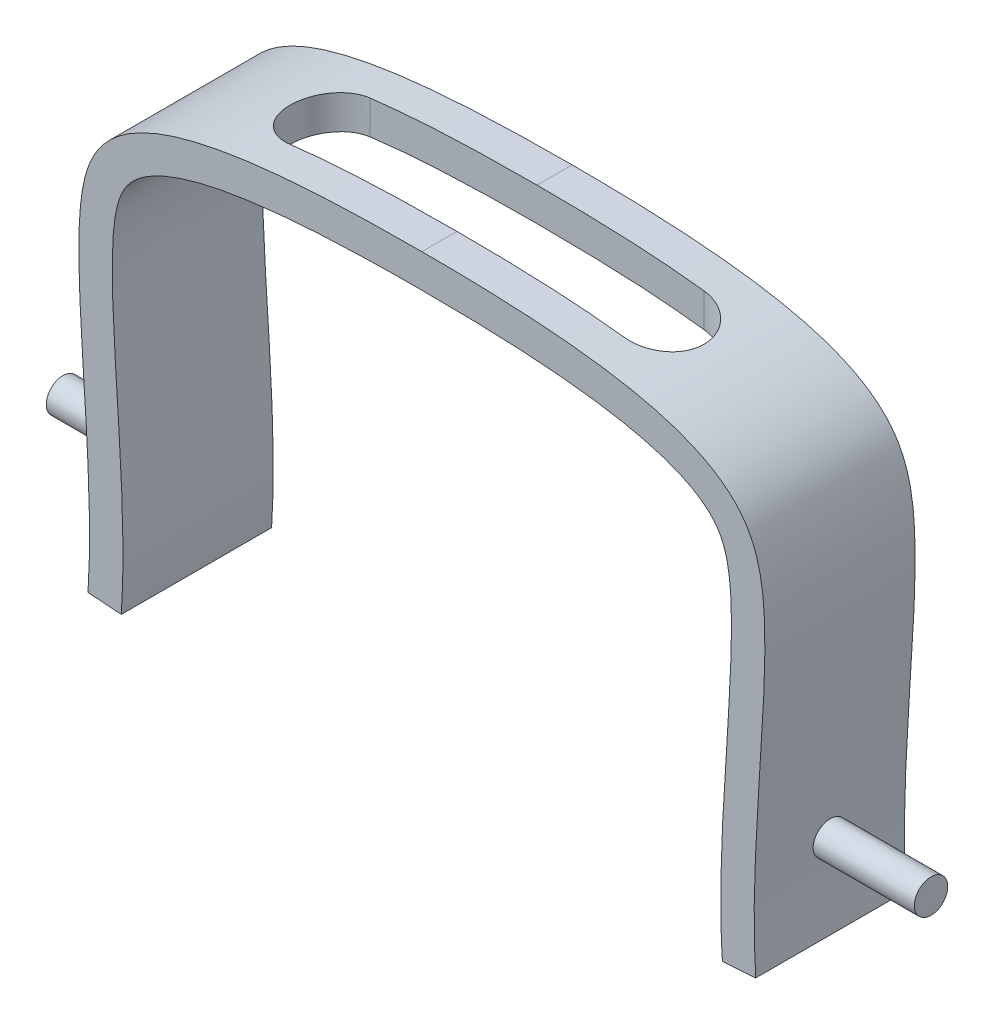
SolidWorks part; units mm, degrees
ref_plane "Front Plane" through (0, 0, 0) normal (0, 0, 1) x (1, 0, 0)
ref_plane "Top Plane" through (0, 0, 0) normal (0, 1, 0) x (1, 0, 0)
ref_plane "Right Plane" through (0, 0, 0) normal (1, 0, 0) x (0, 0, -1)
sketch "Sketch3" plane through (0, 0, 0) normal (0, 0, 1) x (1, 0, 0)
  line L0 (-25.3926, 0.4128) -> (-22.8588, 0.2357)
  line L1 (0, 0) -> (0, 49.1985) construction
  line L2 (22.8588, 0.2357) -> (25.3926, 0.4128)
  spline S0 degree 3 poles (-22.8588, 0.2357) (-22.2073, 9.561) (-24.8571, 24.7477) (-20.4286, 32.2593) (-9.2595, 33.02) (0, 33.02) knots 0 0 0 0 0.433889 0.533889 1 1 1 1
  spline S1 degree 1 poles (-25.3926, 0.4128) (0, 35.56) knots 0 0 1 1 construction
  spline S2 degree 3 poles (22.8588, 0.2357) (22.2073, 9.561) (24.8571, 24.7477) (20.4286, 32.2593) (9.2595, 33.02) (0, 33.02) knots 0 0 0 0 0.433889 0.533889 1 1 1 1
  spline S3 degree 1 poles (25.3926, 0.4128) (0, 35.56) knots 0 0 1 1 construction
  spline S4 degree 3 poles (-25.3926, 0.4128) (-25.3472, 1.0633) (-25.2873, 2.3429) (-25.2559, 5.0926) (-25.3636, 8.6726) (-25.623, 13.0382) (-25.906, 17.2716) (-26.1042, 21.2032) (-26.0979, 24.6856) (-25.8161, 27.1655) (-25.2212, 28.9768) (-24.5105, 30.2231) (-23.5816, 31.2478) (-22.1911, 32.3246) (-20.1914, 33.3182) (-17.4516, 34.1574) (-13.3644, 34.9503) (-8.7163, 35.3649) (-3.7754, 35.5373) (-1.2543, 35.56) (0, 35.56) knots 0 0 0 0 0.03125 0.0625 0.125 0.1875 0.25 0.3125 0.375 0.4375 0.46875 0.5 0.53125 0.5625 0.625 0.6875 0.75 0.875 0.9375 1 1 1 1
  spline S5 degree 3 poles (0, 35.56) (1.2543, 35.56) (3.7754, 35.5373) (8.7163, 35.3649) (13.3644, 34.9503) (17.4516, 34.1574) (20.1914, 33.3182) (22.1911, 32.3246) (23.5816, 31.2478) (24.5105, 30.2231) (25.2212, 28.9768) (25.8161, 27.1655) (26.0979, 24.6856) (26.1042, 21.2032) (25.906, 17.2716) (25.623, 13.0382) (25.3636, 8.6726) (25.2559, 5.0926) (25.2873, 2.3429) (25.3472, 1.0633) (25.3926, 0.4128) knots 0 0 0 0 0.0625 0.125 0.25 0.3125 0.375 0.4375 0.46875 0.5 0.53125 0.5625 0.625 0.6875 0.75 0.8125 0.875 0.9375 0.96875 1 1 1 1
  dimension "D1" = 22.86
  dimension "D2" = 33.02
  dimension "D3" = 2.54
extrude "main body" add sketch "Sketch3" along normal mid plane 11.43
ref_plane "top of rounded bit" through (0, 35.56, 0) normal (0, 1, 0) x (1, 0, 0)
sketch "Sketch4" plane through (0, 35.56, 0) normal (0, 1, 0) x (1, 0, 0)
  line L0 (-12.7, 0) -> (12.7, 0) construction
  line L1 (0, -5.715) -> (0, 5.715) construction
  line L2 (-12.7, 3.048) -> (12.7, 3.048)
  line L3 (-12.7, -3.048) -> (12.7, -3.048)
  arc A0 (-12.7, 3.048) -> (-12.7, -3.048) centre (-12.7, 0) ccw
  arc A1 (12.7, -3.048) -> (12.7, 3.048) centre (12.7, 0) ccw
  point P4 (0, 0)
extrude "slot for joystick" cut sketch "Sketch4" against normal blind 127 and the other way blind 127
ref_plane "nibble plane one" through (-25.3926, 0, 0) normal (1, 0, 0) x (0, 0, -1)
ref_plane "nibble plane two" through (25.3926, 0, 0) normal (1, 0, 0) x (0, 0, -1)
sketch "Sketch5" plane through (25.3926, 0, 0) normal (1, 0, 0) x (0, 0, -1)
  line L0 (-5.715, 0.4128) -> (5.715, 0.4128) construction
  circle A0 centre (0, 6.7628) radius 1.27
  point P2 (0, 0.4128)
  dimension "D1" = 6.35
extrude "nibble two" add sketch "Sketch5" along normal blind 7.62 and the other way up to body
sketch "Sketch6" plane through (-25.3926, 0, 0) normal (1, 0, 0) x (0, 0, -1)
  line L0 (-5.715, 0.4128) -> (5.715, 0.4128) construction
  circle A0 centre (0, 6.7628) radius 1.27
  point P2 (0, 0.4128)
  dimension "D1" = 6.35
extrude "nibble one" add sketch "Sketch6" against normal blind 7.62 and the other way up to body
ref_point "nibble center"
ref_plane "nibble flag plane" through (0, 6.7628, 0) normal (0, 1, 0) x (1, 0, 0)
sketch "Sketch7" plane through (0, 6.7628, 0) normal (0, 1, 0) x (1, 0, 0)
  line L1 (-31.3343, 0.6195) -> (-27.5243, 0.6195)
  line L2 (-31.3343, 0.6195) -> (-31.3343, -0.6505)
  line L3 (-31.3343, -0.6505) -> (-27.5243, -0.6505)
  line L4 (-27.5243, 0.6195) -> (-27.5243, -0.6505)
  line L5 (-31.3343, 0.6195) -> (-27.5243, -0.6505) construction
  line L6 (-31.3343, -0.6505) -> (-27.5243, 0.6195) construction
  point P0 (-29.4293, -0.0155)
  dimension "D1" = 1.27
  dimension "D2" = 3.81
extrude "flag" add sketch "Sketch7" against normal blind 0.254
